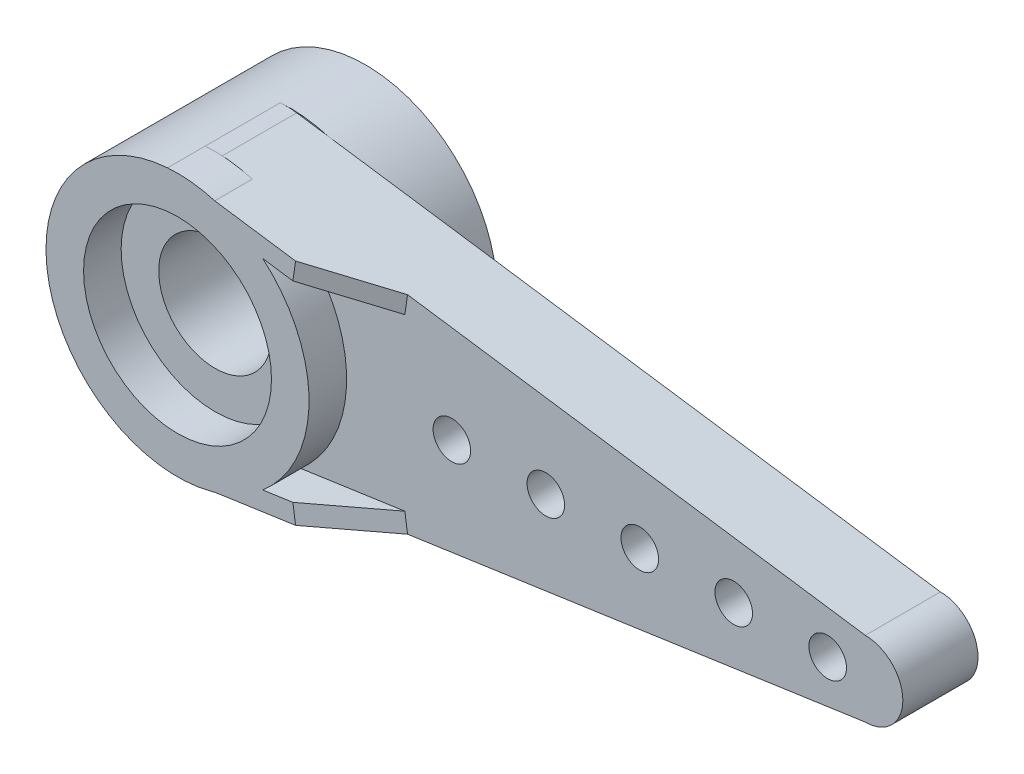
SolidWorks part; units mm, degrees
ref_plane "前视基准面" through (0, 0, 0) normal (0, 0, 1) x (1, 0, 0)
ref_plane "上视基准面" through (0, 0, 0) normal (0, 1, 0) x (1, 0, 0)
ref_plane "右视基准面" through (0, 0, 0) normal (1, 0, 0) x (0, 0, -1)
sketch "草图1" plane through (0, 0, 0) normal (0, 0, 1) x (1, 0, 0)
  circle A0 centre (0, 0) radius 35
  circle A1 centre (0, 0) radius 25
  dimension "D1" = 70
  dimension "D2" = 50
extrude "凸台-拉伸1" add sketch "草图1" along normal blind 20
sketch "草图2" plane through (0, 0, 20) normal (0, 0, 1) x (1, 0, 0)
  line L0 (0, 0) -> (150, 0) construction
  line L1 (0, 35) -> (173, 10)
  line L2 (0, -35) -> (173, -10)
  arc A0 (0, 35) -> (0, -35) centre (0, 0) ccw
  arc A1 (173, -10) -> (173, 10) centre (173, 0) ccw
  dimension "D2" = 20
  dimension "D1" = 173
extrude "凸台-拉伸2" add sketch "草图2" along normal blind 20
sketch "草图3" plane through (0, 0, 40) normal (0, 0, 1) x (1, 0, 0)
  circle A0 centre (0, 0) radius 15
  dimension "D1" = 30
extrude "切除-拉伸1" cut sketch "草图3" against normal blind 20
sketch "草图4" plane through (0, 0, 40) normal (0, 0, 1) x (1, 0, 0)
  circle A0 centre (0, 0) radius 35
  dimension "D1" = 70
extrude "凸台-拉伸3" add sketch "草图4" along normal blind 10
sketch "草图5" plane through (0, 0, 50) normal (0, 0, 1) x (1, 0, 0)
  circle A0 centre (0, 0) radius 15
  dimension "D1" = 30
extrude "切除-拉伸2" cut sketch "草图5" against normal blind 10
sketch "草图6" plane through (0, 0, 50) normal (0, 0, 1) x (1, 0, 0)
  circle A0 centre (0, 0) radius 25
extrude "切除-拉伸3" cut sketch "草图6" against normal blind 10
fillet "圆角1" radius 20 1 edges at (0, 35, 30)
fillet "圆角2" radius 20 1 edges at (0, -35, 30)
sketch "草图7" plane through (0, 0, 40) normal (0, 0, 1) x (1, 0, 0)
  circle A0 centre (163, 0) radius 5
  arc A1 (173, -10) -> (173, 10) centre (173, 0) ccw construction
  circle A2 centre (138, 0) radius 5
  circle A3 centre (113, 0) radius 5
  circle A4 centre (88, 0) radius 5
  circle A5 centre (63, 0) radius 5
  point P5 (183, 0)
  dimension "D1" = 10
  dimension "D3" = 10
  dimension "D5" = 10
  dimension "D8" = 10
  dimension "D9" = 10
  dimension "D2" = 20
  dimension "D4" = 25
  dimension "D6" = 25
  dimension "D7" = 25
  dimension "D10" = 25
extrude "切除-拉伸4" cut sketch "草图7" against normal blind 20
sketch "草图10" plane through (4.9543, -34.2841, 0) normal (0.143, -0.9897, 0) x (0.9897, 0.143, 0)
  line L0 (-3.2658, 40) -> (46.7342, 40)
  line L1 (5.0058, 40) -> (169.7912, 40) construction
  line L2 (46.7342, 40) -> (26.7342, 50)
  line L3 (26.7342, 50) -> (-3.2658, 50)
  line L4 (25, 50) -> (-25, 50) construction
  line L5 (-3.2658, 50) -> (-3.2658, 40)
  dimension "D1" = 50
  dimension "D2" = 30
extrude "凸台-拉伸10" add sketch "草图10" against normal blind 5
fillet "圆角3" radius 20 1 edges at (9.9087, -33.5681, 45)
sketch "草图11" plane through (4.9543, 34.2841, 0) normal (0.143, 0.9897, 0) x (0.9897, -0.143, 0)
  line L0 (-3.2658, -40) -> (46.7342, -40)
  line L1 (169.7912, -40) -> (5.0058, -40) construction
  line L2 (46.7342, -40) -> (26.7342, -50)
  line L3 (-35, -50) -> (35, -50) construction
  line L4 (26.7342, -50) -> (-3.2658, -50)
  line L5 (-3.2658, -50) -> (-3.2658, -40)
  dimension "D1" = 50
  dimension "D2" = 30
extrude "凸台-拉伸12" add sketch "草图11" against normal blind 5
scale "缩放比例1" scale about centroid uniform scaling yes scale factor 0.1
